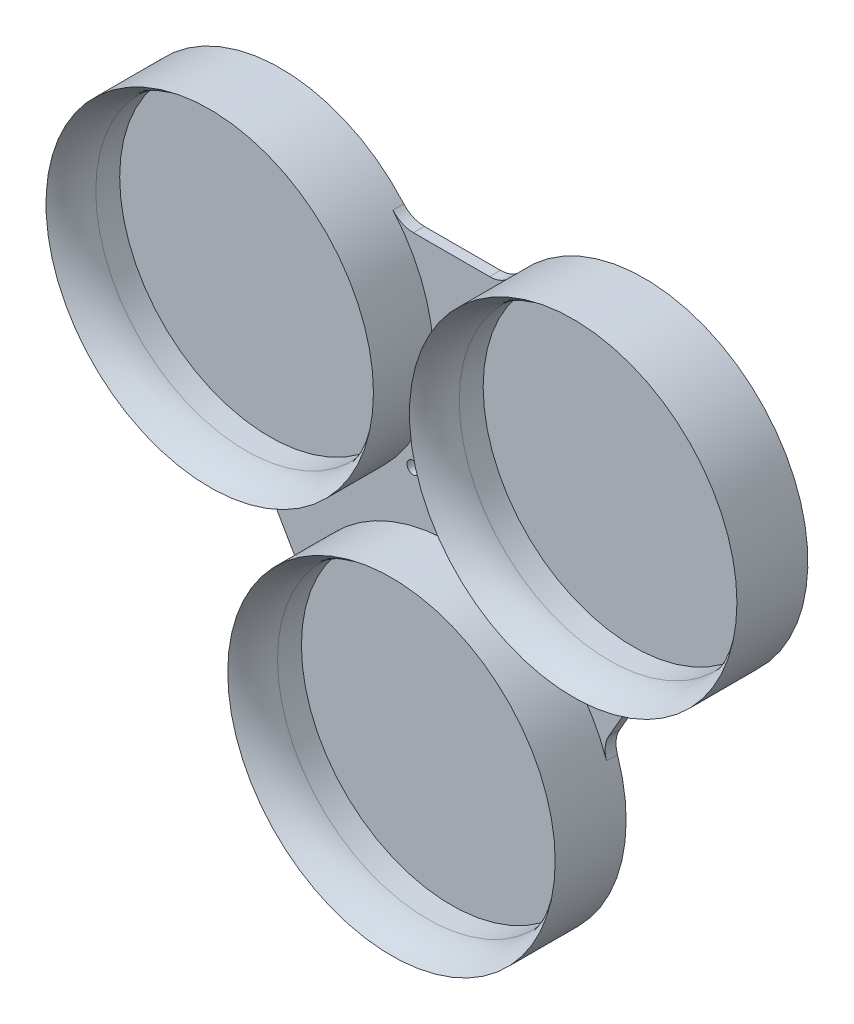
SolidWorks part; units mm, degrees
ref_plane "前视基准面" through (0, 0, 0) normal (0, 0, 1) x (1, 0, 0)
ref_plane "上视基准面" through (0, 0, 0) normal (0, 1, 0) x (1, 0, 0)
ref_plane "右视基准面" through (0, 0, 0) normal (1, 0, 0) x (0, 0, -1)
other "Configuration Table"
sketch "草图1" plane through (0, 0, 0) normal (0, 0, 1) x (1, 0, 0)
  line L0 (0, 0) -> (66.6, 0) construction
  line L1 (66.6, 0) -> (33.3, -57.6773) construction
  line L2 (33.3, -57.6773) -> (0, 0) construction
  circle A0 centre (0, 0) radius 27.5
  circle A1 centre (0, 0) radius 30
  circle A2 centre (66.6, 0) radius 30
  circle A3 centre (66.6, 0) radius 27.5
  circle A4 centre (33.3, -57.6773) radius 30
  circle A5 centre (33.3, -57.6773) radius 27.5
  dimension "D1" = 66.6
  dimension "D2" = 66.6
  dimension "D3" = 66.6
extrude "凸台-拉伸1" add sketch "草图1" along normal blind 13
sketch "草图2" plane through (0, 0, 0) normal (0, 0, 1) x (1, 0, 0)
  line L4 (26.3199, 18.0708) -> (40.2801, 18.0708)
  line L6 (69.0899, -31.8291) -> (62.1097, -43.919)
  line L8 (4.4903, -43.919) -> (-2.4899, -31.8291)
  arc A10 (22.5599, 19.775) -> (-5.8457, -29.425) centre (0, 0) ccw
  arc A11 (72.4457, -29.425) -> (44.0401, 19.775) centre (66.6, 0) ccw
  arc A12 (4.8944, -48.0273) -> (61.7056, -48.0273) centre (33.3, -57.6773) ccw
  arc A14 (4.8944, -48.0273) -> (4.4903, -43.919) centre (0.1601, -46.419) ccw
  arc A16 (-2.4899, -31.8291) -> (-5.8457, -29.425) centre (-6.82, -34.3291) ccw
  arc A17 (62.1097, -43.919) -> (61.7056, -48.0273) centre (66.4399, -46.419) ccw
  arc A18 (72.4457, -29.425) -> (69.0899, -31.8291) centre (73.42, -34.3291) ccw
  arc A19 (40.2801, 18.0708) -> (44.0401, 19.775) centre (40.2801, 23.0708) ccw
  arc A20 (26.3199, 18.0708) -> (22.5599, 19.775) centre (26.3199, 23.0708) cw
  dimension "D1" = 5
extrude "凸台-拉伸2" add sketch "草图2" along normal blind 2
sketch "草图3" plane through (0, 0, 0) normal (0, 0, 1) x (1, 0, 0)
  circle A0 centre (33.3, -57.6773) radius 27.5 construction
  circle A1 centre (66.6, 0) radius 27.5 construction
  circle A4 centre (33.3, -19.2258) radius 38.4515 construction
  circle A5 centre (33.3, -19.2258) radius 1.15
  circle A6 centre (33.3, -19.2258) radius 7 construction
  circle A7 centre (33.3, -12.2258) radius 1.15
  circle A8 centre (40.3, -19.2258) radius 1.15
  circle A9 centre (33.3, -26.2258) radius 1.15
  circle A10 centre (26.3, -19.2258) radius 1.15
  dimension "D1" = 14
  dimension "D2" = 2.3
  dimension "D3" = 2.3
  dimension "D4" = 14
extrude "切除-拉伸5" cut sketch "草图3" along normal through all
fillet "圆角1" radius 10 3 edges at (94.1, 0, 13) (27.5, 0, 13) (60.8, -57.6773, 13)
sketch "草图4" plane through (0, 0, 0) normal (0, 0, -1) x (-1, 0, 0)
  circle A0 centre (-33.3, -19.2258) radius 23.8475
sketch "草图5" plane through (0, 0, 0) normal (0, 0, -1) x (-1, 0, 0)
  circle A0 centre (-33.3, -19.2258) radius 10.5
  circle A1 centre (-33.3, -19.2258) radius 12.5
  dimension "D1" = 25
  dimension "D2" = 21
extrude "凸台-拉伸3" add sketch "草图5" along normal blind 7
